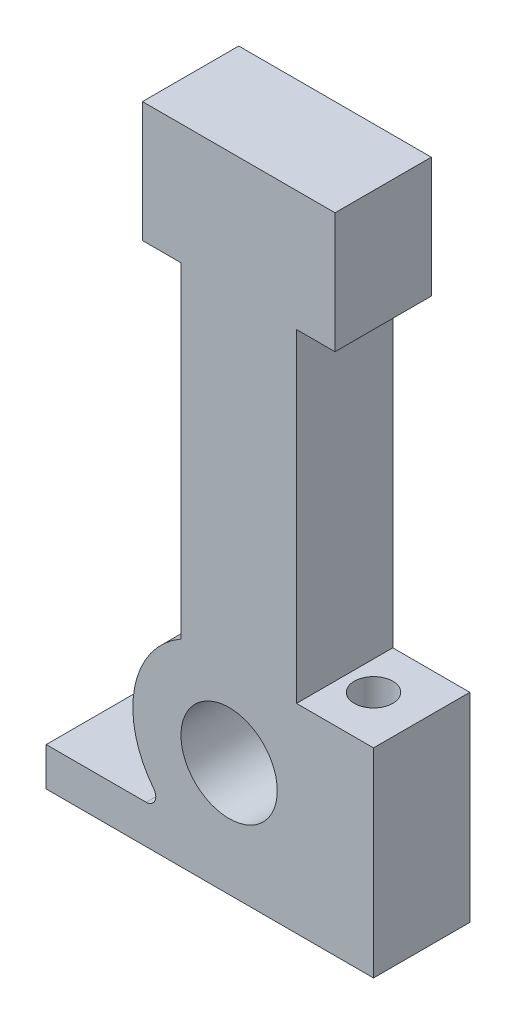
SolidWorks part; units mm, degrees
material "6061 Alloy"
ref_plane "Front Plane" through (0, 0, 0) normal (0, 0, 1) x (1, 0, 0)
ref_plane "Top Plane" through (0, 0, 0) normal (0, 1, 0) x (1, 0, 0)
ref_plane "Right Plane" through (0, 0, 0) normal (1, 0, 0) x (0, 0, -1)
sketch "Sketch2" plane through (0, 0, 0) normal (0, 0, 1) x (1, 0, 0)
  line L1 (-6.9033, 33.4448) -> (8.3367, 33.4448)
  line L2 (-3.7283, 17.5698) -> (-3.7283, -25.4066)
  line L4 (11.5117, 17.5698) -> (11.5117, -25.1475)
  line L8 (21.6717, -25.1475) -> (21.6717, -51.4365)
  line L9 (11.5117, -25.1475) -> (21.6717, -25.1475)
  line L10 (-3.7283, 17.5698) -> (-8.8083, 17.5698)
  line L11 (-8.8083, 17.5698) -> (-8.8083, 33.4448)
  line L12 (-8.8083, 33.4448) -> (-6.9033, 33.4448)
  line L13 (11.5117, 17.5698) -> (16.5917, 17.5698)
  line L14 (16.5917, 17.5698) -> (16.5917, 33.4448)
  line L15 (16.5917, 33.4448) -> (8.3367, 33.4448)
  line L16 (21.6717, -51.4365) -> (1.3517, -51.4365)
  line L19 (1.3517, -51.4365) -> (-21.5083, -51.4365)
  line L20 (-21.5083, -51.4365) -> (-21.5083, -46.3565)
  line L21 (-21.5083, -46.3565) -> (-5.2688, -46.3565)
  circle A0 centre (2.6217, -36.4052) radius 6.35
  arc A1 (-5.2688, -46.3565) -> (-3.7283, -25.4066) centre (2.6217, -36.4052) cw
  dimension "D2" = 8.89
  dimension "D13" = 6.35
  dimension "D14" = 12.7
  dimension "D1" = 15.24
  dimension "D3" = 69.85
  dimension "D4" = 20.32
  dimension "D5" = 26.289
  dimension "D6" = 10.16
  dimension "D7" = 15.875
  dimension "D8" = 25.4
  dimension "D9" = 5.08
  dimension "D10" = 15.24
  dimension "D11" = 5.08
  dimension "D12" = 22.86
extrude "Boss-Extrude1" add sketch "Sketch2" along normal blind 12.7
sketch "Sketch3" plane through (0, -25.1475, 0) normal (0, 1, 0) x (1, 0, 0)
  line L0 (21.6717, -12.7) -> (11.5117, -12.7) construction
  line L2 (11.5117, -12.7) -> (11.5117, 0) construction
  circle A0 centre (15.3217, -6.35) radius 2.54
  circle A1 centre (-10.0783, -6.35) radius 2.54
  point P8 (0, 0)
  dimension "D2" = 3.81
  dimension "D3" = 5.08
  dimension "D1" = 6.35
  dimension "D4" = 25.4
extrude "Cut-Extrude1" cut sketch "Sketch3" against normal blind 38.1
fillet "Fillet1" radius 1.27 1 edges at (-5.2688, -46.3565, 6.35)
sketch "Sketch4" plane through (0, -25.1475, 0) normal (0, 1, 0) x (1, 0, 0)
  line L0 (21.6717, -12.7) -> (11.5117, -12.7) construction
  line L1 (21.6717, -12.7) -> (21.6717, 0) construction
  circle A0 centre (-10.0783, -6.35) radius 3.175
  dimension "D1" = 6.35
  dimension "D2" = 6.35
  dimension "D3" = 31.75
extrude "Cut-Extrude2" cut sketch "Sketch4" against normal blind 20.32
